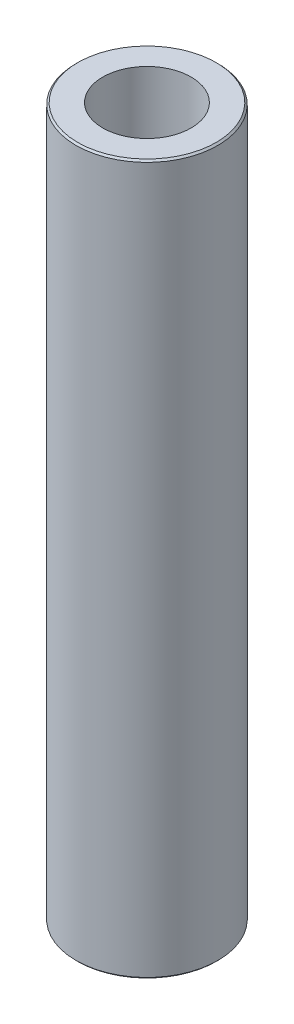
SolidWorks part; units mm, degrees
ref_plane "Front Plane" through (0, 0, 0) normal (0, 0, 1) x (1, 0, 0)
ref_plane "Top Plane" through (0, 0, 0) normal (0, 1, 0) x (1, 0, 0)
ref_plane "Right Plane" through (0, 0, 0) normal (1, 0, 0) x (0, 0, -1)
sketch "Sketch1" plane through (0, 0, 0) normal (0, 1, 0) x (1, 0, 0)
  circle A0 centre (0, 0) radius 60
  dimension "SHAFT_OD" = 120
extrude "Boss-Extrude1" add sketch "Sketch1" along normal blind 600
sketch "Sketch2" plane through (0, 0, 0) normal (0, 1, 0) x (1, 0, 0)
  circle A0 centre (0, 0) radius 37.3742
  dimension "BORE_D" = 74.7484
extrude "Cut-Extrude1" cut sketch "Sketch2" along normal through all
chamfer "Chamfer1" distance 1.4511 angle 45 2 edges at (0, 600, 60) (0, 0, 60)
